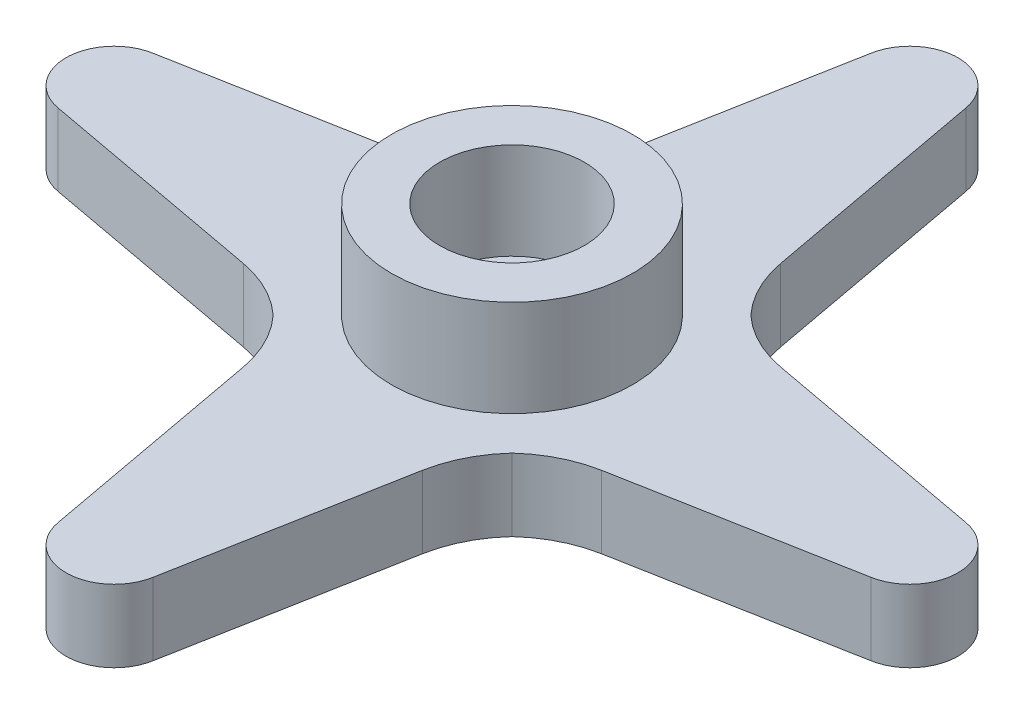
SolidWorks part; units mm, degrees
ref_plane "Front Plane" through (0, 0, 0) normal (0, 0, 1) x (1, 0, 0)
ref_plane "Top Plane" through (0, 0, 0) normal (0, 1, 0) x (1, 0, 0)
ref_plane "Right Plane" through (0, 0, 0) normal (1, 0, 0) x (0, 0, -1)
sketch "Sketch1" plane through (0, 0, 0) normal (0, 1, 0) x (1, 0, 0)
  line L0 (-1.9667, 16.8636) -> (-4.0259, 5.7264)
  line L1 (1.9667, 16.8636) -> (4.0259, 5.7264)
  line L2 (16.8636, -1.9667) -> (5.7264, -4.0259)
  line L3 (16.8636, 1.9667) -> (5.7264, 4.0259)
  line L4 (-1.9667, -16.8636) -> (-4.0259, -5.7264)
  line L5 (1.9667, -16.8636) -> (4.0259, -5.7264)
  line L6 (-16.8636, 1.9667) -> (-5.7264, 4.0259)
  line L7 (-16.8636, -1.9667) -> (-5.7264, -4.0259)
  circle A0 centre (0, 0) radius 18.5 construction
  arc A1 (-4.0259, 5.7264) -> (-5.7264, 4.0259) centre (0, 0) ccw
  circle A2 centre (0, 0) radius 5 construction
  arc A3 (1.9667, 16.8636) -> (-1.9667, 16.8636) centre (0, 16.5) ccw
  arc A4 (16.8636, -1.9667) -> (16.8636, 1.9667) centre (16.5, 0) ccw
  arc A5 (-1.9667, -16.8636) -> (1.9667, -16.8636) centre (0, -16.5) ccw
  arc A6 (-16.8636, 1.9667) -> (-16.8636, -1.9667) centre (-16.5, 0) ccw
  arc A7 (-5.7264, -4.0259) -> (-4.0259, -5.7264) centre (0, 0) ccw
  arc A8 (4.0259, -5.7264) -> (5.7264, -4.0259) centre (0, 0) ccw
  arc A9 (5.7264, 4.0259) -> (4.0259, 5.7264) centre (0, 0) ccw
  point P27 (0, 0)
  dimension "D1" = 37
  dimension "D2" = 14
  dimension "D3" = 10
  dimension "D4" = 4
  dimension "D5" = 4
extrude "Boss-Extrude1" add sketch "Sketch1" along normal blind 3
sketch "Sketch2" plane through (0, 3, 0) normal (0, 1, 0) x (1, 0, 0)
  circle A0 centre (0, 0) radius 5
  dimension "D1" = 10
extrude "Boss-Extrude2" add sketch "Sketch2" along normal blind 4
sketch "Sketch3" plane through (0, 7, 0) normal (0, 1, 0) x (1, 0, 0)
  circle A0 centre (0, 0) radius 3
  dimension "D1" = 6
extrude "Cut-Extrude1" cut sketch "Sketch3" against normal blind 4
fillet "Fillet1" radius 5 8 edges at (5.7264, 1.5, 4.0259) (4.0259, 1.5, 5.7264) (-4.0259, 1.5, 5.7264) (-5.7264, 1.5, 4.0259) (-5.7264, 1.5, -4.0259) (-4.0259, 1.5, -5.7264) (5.7264, 1.5, -4.0259) (4.0259, 1.5, -5.7264)
